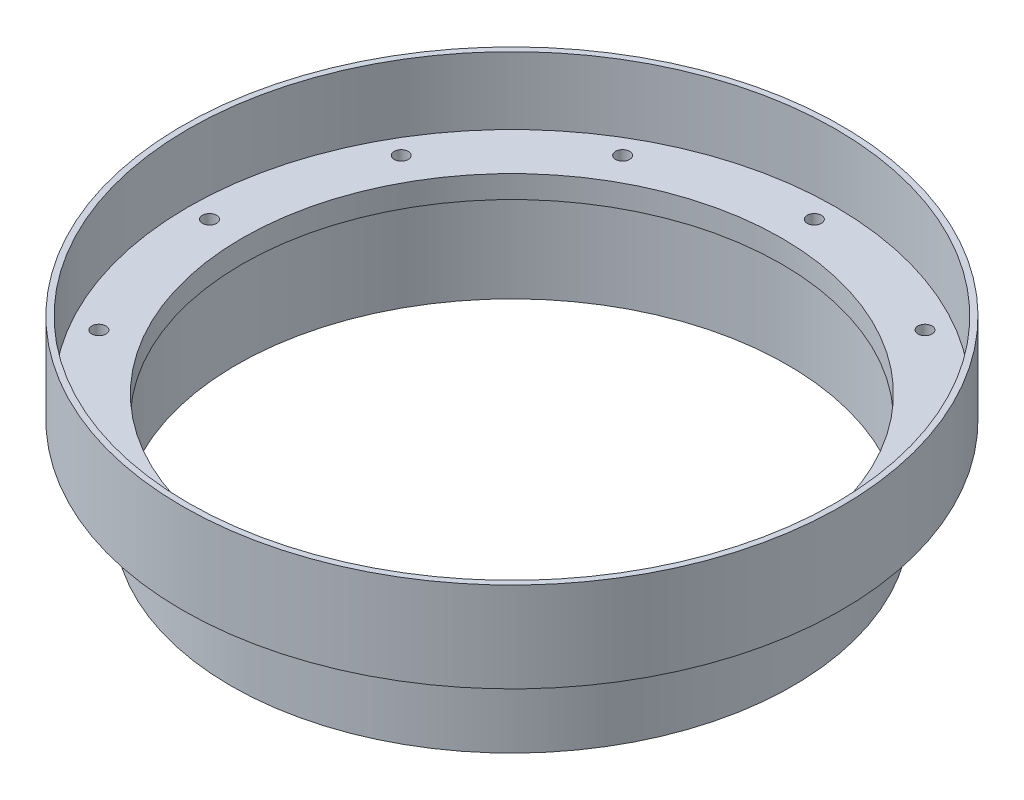
SolidWorks part; units mm, degrees
material "6061-T6 (SS)"
ref_plane "Front Plane" through (0, 0, 0) normal (0, 0, 1) x (1, 0, 0)
ref_plane "Top Plane" through (0, 0, 0) normal (0, 1, 0) x (1, 0, 0)
ref_plane "Right Plane" through (0, 0, 0) normal (1, 0, 0) x (0, 0, -1)
ref_axis "Axis1" through (0, 55, 0) along (0, -1, 0)
sketch "Cross Section" plane through (0, 0, 0) normal (0, 0, 1) x (1, 0, 0)
  line L0 (-38.1, 0) -> (-38.1, -3.175)
  line L1 (-38.1, -3.175) -> (-38.8874, -3.175)
  line L2 (-38.8874, -3.175) -> (-38.8874, -15.875)
  line L4 (0, -15.875) -> (-38.1, -15.875) construction
  line L5 (-39.6812, -15.875) -> (-39.6812, -3.175)
  line L6 (-39.6812, -3.175) -> (-46.5392, -3.175)
  line L7 (-46.5392, -3.175) -> (-46.5392, 9.525)
  line L8 (-46.5392, 9.525) -> (-45.72, 9.525)
  line L9 (-45.72, 9.525) -> (-45.72, 0)
  line L10 (-45.72, 0) -> (-38.1, 0)
  line L11 (-38.1, 0) -> (0, 0) construction
  line L12 (0, 55) -> (0, -55) construction
  line L13 (-38.8874, -15.875) -> (-39.6812, -15.875)
  line L14 (-45.72, 1.5875) -> (-45.72, 3.175) construction
  dimension "D1" = 0.7874
  dimension "D3" = 0.7937
  dimension "D5" = 6.858
  dimension "D6" = 12.7
  dimension "D9" = 3.175
  dimension "D8" = 38.1
revolve "Main" add sketch "Cross Section" angle 360 about axis through (0, 55, 0) along (0, -1, 0)
sketch "Hole Location" plane through (0, 0, 0) normal (0, 1, 0) x (1, 0, 0)
  line L0 (0, 0) -> (-42.7006, 0) construction
  circle A0 centre (0, 0) radius 42.7006 construction
  dimension "D1" = 85.4012
hole_wizard "#3-48 Tapped Hole1" positions "Sketch5" profile "Sketch7" tap size "#3-48" standard "ANSI Inch"
sketch "Sketch5" plane through (0, 0, 0) normal (0, 1, 0) x (1, 0, 0)
  point P0 (-42.7006, 0)
sketch "Sketch7" plane through (-42.7006, 0, 0) normal (1, 0, 0) x (0, 0, 1)
  line L0 (0, 0) -> (0, 3.901)
  line L1 (0, 3.901) -> (0.9969, 3.302)
  line L2 (0.9969, 3.302) -> (0.9969, 0)
  line L5 (0.9969, 0) -> (0, 0)
  line L10 (0, 3.901) -> (-0.997, 3.302) construction
  line L11 (0, -6.35) -> (0, 107.95) construction
  dimension "Tap Drill Dia." = 1.9939
  dimension "Tap Drill Depth" = 3.302
  dimension "Drill Angle" = 118
cosmetic thread "Hole Thread1" parameters "D1"=3.175, "D2"=2.5146
pattern_circular "Screw Holes" count 12 over 360 about axis through (0, 55, 0) along (0, -1, 0) of "#3-48 Tapped Hole1"
equation "\"D8@Cross Section\"=\"TANK DIAMETER@Cryo Tank.Assembly\"/2"
equation "\"D1@Hole Location\"=\"TANK DIAMETER@Cryo Tank.Assembly\"+\"GASKET SEAT THICKNESS@Cryo Tank.Assembly\"+\"LINER THICKNESS@Cryo Tank.Assembly\"+\"ALUMINUM LAP THICKNESS@Cryo Tank.Assembly\""
equation "\"D1@Cross Section\"=\"LINER THICKNESS@Cryo Tank.Assembly\""
equation "\"D3@Cross Section\"=\"ALUMINUM LAP THICKNESS@Cryo Tank.Assembly\""
equation "\"D5@Cross Section\"=2*\"CF THICKNESS@Cryo Tank.Assembly\"+\"NOMEX THICKNESS@Cryo Tank.Assembly\""
